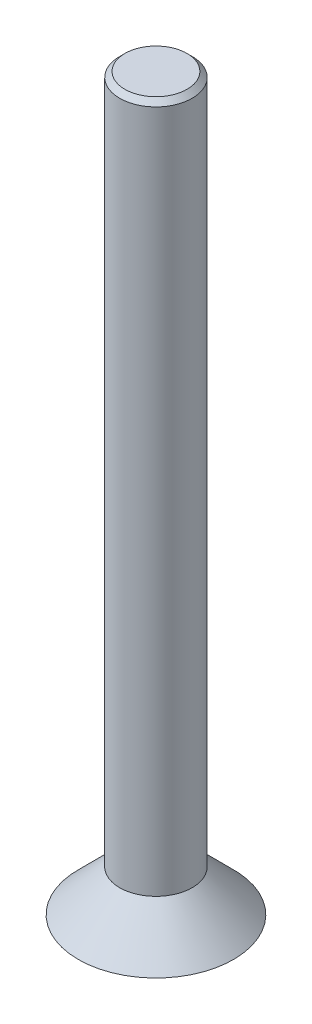
SolidWorks part; units mm, degrees
material "铸造合金钢"
ref_plane "前视基准面" through (0, 0, 0) normal (0, 0, 1) x (1, 0, 0)
ref_plane "上视基准面" through (0, 0, 0) normal (0, 1, 0) x (1, 0, 0)
ref_plane "右视基准面" through (0, 0, 0) normal (1, 0, 0) x (0, 0, -1)
sketch "草图1" plane through (0, 0, 0) normal (0, 1, 0) x (1, 0, 0)
  line L1 (0, -1.1547) -> (1, -0.5774)
  line L2 (1, -0.5774) -> (1, 0.5774)
  line L3 (1, 0.5774) -> (0, 1.1547)
  line L4 (0, 1.1547) -> (-1, 0.5774)
  line L5 (-1, 0.5774) -> (-1, -0.5774)
  line L6 (-1, -0.5774) -> (0, -1.1547)
  circle A0 centre (0, 0) radius 3
  circle A1 centre (0, 0) radius 1 construction
  dimension "D1" = 6
  dimension "D2" = 2
extrude "凸台-拉伸1" add sketch "草图1" along normal blind 1.6
chamfer "倒角1" distance 1.6 angle 45 1 edges at (0, 1.6, 3)
sketch "草图2" plane through (0, 1.6, 0) normal (0, 1, 0) x (1, 0, 0)
  circle A0 centre (0, 0) radius 1.4
  dimension "D1" = 2.8
extrude "凸台-拉伸2" add sketch "草图2" along normal blind 26.6
chamfer "倒角2" distance 0.2 angle 45 1 edges at (0, 28.2, 1.4)
